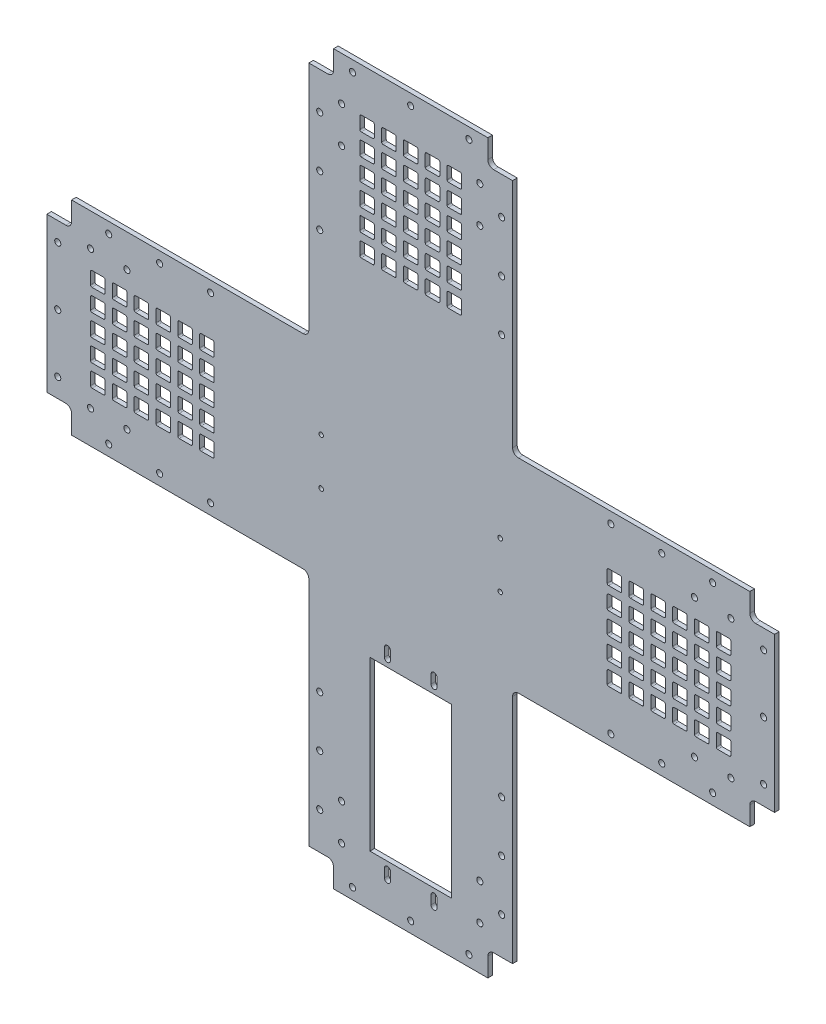
SolidWorks part; units mm, degrees
ref_plane "Front Plane" through (0, 0, 0) normal (0, 0, 1) x (1, 0, 0)
ref_plane "Top Plane" through (0, 0, 0) normal (0, 1, 0) x (1, 0, 0)
ref_plane "Right Plane" through (0, 0, 0) normal (1, 0, 0) x (0, 0, -1)
sketch "Sketch1" plane through (0, 0, 0) normal (0, 0, 1) x (1, 0, 0)
  line L0 (0, 0) -> (0, 180)
  line L1 (0, 180) -> (140, 180)
  line L2 (140, 180) -> (140, 0)
  line L3 (140, 0) -> (320, 0)
  line L4 (320, 0) -> (320, -140)
  line L5 (320, -140) -> (140, -140)
  line L6 (140, -140) -> (140, -320)
  line L7 (140, -320) -> (0, -320)
  line L8 (0, -320) -> (0, -140)
  line L9 (0, -140) -> (-180, -140)
  line L10 (-180, -140) -> (-180, 0)
  line L11 (-180, 0) -> (0, 0)
  line L12 (70, 180) -> (70, -320) construction
  line L13 (0, 180) -> (17, 180)
  line L14 (0, 180) -> (0, 163)
  line L15 (0, 163) -> (17, 163)
  line L16 (17, 180) -> (17, 163)
  line L17 (-180, -70) -> (320, -70) construction
  line L18 (140, 0) -> (0, -140) construction
  line L19 (0, 0) -> (140, -140) construction
  line L20 (7.5, 137.5) -> (7.5, 67.5) construction
  line L21 (140, 180) -> (123, 180)
  line L22 (140, 180) -> (140, 163)
  line L23 (140, 163) -> (123, 163)
  line L24 (123, 180) -> (123, 163)
  line L25 (-180, 0) -> (-163, 0)
  line L26 (-180, 0) -> (-180, -17)
  line L27 (-180, -17) -> (-163, -17)
  line L28 (-163, 0) -> (-163, -17)
  line L29 (-180, -140) -> (-163, -140)
  line L30 (-180, -140) -> (-180, -123)
  line L31 (-180, -123) -> (-163, -123)
  line L32 (-163, -140) -> (-163, -123)
  line L33 (320, 0) -> (303, 0)
  line L34 (320, 0) -> (320, -17)
  line L35 (320, -17) -> (303, -17)
  line L36 (303, 0) -> (303, -17)
  line L37 (320, -140) -> (303, -140)
  line L38 (320, -140) -> (320, -123)
  line L39 (320, -123) -> (303, -123)
  line L40 (303, -140) -> (303, -123)
  line L41 (140, -320) -> (123, -320)
  line L42 (140, -320) -> (140, -303)
  line L43 (140, -303) -> (123, -303)
  line L44 (123, -320) -> (123, -303)
  line L45 (0, -320) -> (17, -320)
  line L46 (0, -320) -> (0, -303)
  line L47 (0, -303) -> (17, -303)
  line L48 (17, -320) -> (17, -303)
  line L49 (22.5, 150) -> (117.5, 150) construction
  line L50 (22.5, 150) -> (22.5, 125) construction
  line L51 (22.5, 125) -> (117.5, 125) construction
  line L52 (117.5, 150) -> (117.5, 125) construction
  line L53 (30, 172.5) -> (110, 172.5) construction
  line L64 (42, -227.325) -> (98, -227.325) construction
  line L69 (42, -169.65) -> (98, -169.65)
  line L70 (42, -169.65) -> (42, -285)
  line L71 (42, -285) -> (98, -285)
  line L72 (98, -169.65) -> (98, -285)
  line L73 (51.95, -290) -> (56.05, -290) construction
  line L74 (51.95, -290) -> (51.95, -296)
  line L75 (51.95, -296) -> (56.05, -296) construction
  line L76 (56.05, -290) -> (56.05, -296)
  line L77 (88.05, -290) -> (88.05, -296)
  line L78 (83.95, -290) -> (83.95, -296)
  line L79 (88.05, -164.65) -> (88.05, -158.65)
  line L80 (83.95, -164.65) -> (83.95, -158.65)
  line L81 (51.95, -164.65) -> (51.95, -158.65)
  line L82 (56.05, -164.65) -> (56.05, -158.65)
  line L83 (8.5, -54) -> (131.5, -86) construction
  line L84 (8.5, -54) -> (131.5, -54) construction
  line L85 (8.5, -54) -> (8.5, -86) construction
  line L86 (8.5, -86) -> (131.5, -86) construction
  line L87 (131.5, -54) -> (131.5, -86) construction
  line L88 (131.5, -54) -> (8.5, -86) construction
  circle A0 centre (22.5, 150) radius 2.1
  circle A1 centre (22.5, 125) radius 2.1
  circle A2 centre (117.5, 150) radius 2.1
  circle A3 centre (117.5, 125) radius 2.1
  circle A4 centre (-125, -117.5) radius 2.1
  circle A5 centre (-150, -117.5) radius 2.1
  circle A6 centre (-125, -22.5) radius 2.1
  circle A7 centre (-150, -22.5) radius 2.1
  circle A8 centre (265, -117.5) radius 2.1
  circle A9 centre (265, -22.5) radius 2.1
  circle A10 centre (290, -22.5) radius 2.1
  circle A11 centre (290, -117.5) radius 2.1
  circle A12 centre (117.5, -290) radius 2.1
  circle A13 centre (117.5, -265) radius 2.1
  circle A14 centre (22.5, -265) radius 2.1
  circle A15 centre (22.5, -290) radius 2.1
  circle A17 centre (7.5, 137.5) radius 2.1
  circle A18 centre (7.5, 67.5) radius 2.1
  circle A19 centre (7.5, 102.5) radius 2.1
  circle A20 centre (30, 172.5) radius 2.1
  circle A21 centre (70, 172.5) radius 2.1
  circle A22 centre (110, 172.5) radius 2.1
  circle A23 centre (132.5, 67.5) radius 2.1
  circle A24 centre (132.5, 102.5) radius 2.1
  circle A25 centre (132.5, 137.5) radius 2.1
  circle A26 centre (207.5, -7.5) radius 2.1
  circle A27 centre (242.5, -7.5) radius 2.1
  circle A28 centre (277.5, -7.5) radius 2.1
  circle A29 centre (312.5, -30) radius 2.1
  circle A30 centre (312.5, -70) radius 2.1
  circle A31 centre (312.5, -110) radius 2.1
  circle A32 centre (277.5, -132.5) radius 2.1
  circle A33 centre (242.5, -132.5) radius 2.1
  circle A34 centre (207.5, -132.5) radius 2.1
  circle A35 centre (-67.5, -132.5) radius 2.1
  circle A36 centre (-102.5, -132.5) radius 2.1
  circle A37 centre (-137.5, -132.5) radius 2.1
  circle A38 centre (-172.5, -110) radius 2.1
  circle A39 centre (-172.5, -70) radius 2.1
  circle A40 centre (-172.5, -30) radius 2.1
  circle A41 centre (-137.5, -7.5) radius 2.1
  circle A42 centre (-102.5, -7.5) radius 2.1
  circle A43 centre (-67.5, -7.5) radius 2.1
  circle A44 centre (7.5, -207.5) radius 2.1
  circle A45 centre (7.5, -242.5) radius 2.1
  circle A46 centre (7.5, -277.5) radius 2.1
  circle A47 centre (30, -312.5) radius 2.1
  circle A48 centre (70, -312.5) radius 2.1
  circle A49 centre (110, -312.5) radius 2.1
  circle A50 centre (132.5, -277.5) radius 2.1
  circle A51 centre (132.5, -242.5) radius 2.1
  circle A52 centre (132.5, -207.5) radius 2.1
  arc A53 (51.95, -290) -> (56.05, -290) centre (54, -290) cw
  arc A54 (51.95, -296) -> (56.05, -296) centre (54, -296) ccw
  arc A55 (88.05, -296) -> (83.95, -296) centre (86, -296) cw
  arc A56 (88.05, -290) -> (83.95, -290) centre (86, -290) ccw
  arc A57 (88.05, -158.65) -> (83.95, -158.65) centre (86, -158.65) ccw
  arc A58 (88.05, -164.65) -> (83.95, -164.65) centre (86, -164.65) cw
  arc A59 (51.95, -158.65) -> (56.05, -158.65) centre (54, -158.65) cw
  arc A60 (51.95, -164.65) -> (56.05, -164.65) centre (54, -164.65) ccw
  circle A61 centre (8.5, -54) radius 1.55
  circle A62 centre (131.5, -54) radius 1.55
  circle A63 centre (131.5, -86) radius 1.55
  circle A64 centre (8.5, -86) radius 1.55
  point P21 (70, -320)
  point P24 (320, -70)
  point P147 (70, -169.65)
  point P197 (70, -70)
  point P198 (70, -70)
  dimension "D29" = 4.2
  dimension "D30" = 4.2
  dimension "D31" = 4.2
  dimension "D32" = 4.2
  dimension "D33" = 4.2
  dimension "D34" = 4.2
  dimension "D35" = 4.2
  dimension "D42" = 4.2
  dimension "D43" = 4.2
  dimension "D44" = 4.2
  dimension "D59" = 3.1
  dimension "D60" = 3.1
  dimension "D61" = 3.1
  dimension "D62" = 3.1
  dimension "D1" = 140
  dimension "D2" = 140
  dimension "D3" = 140
  dimension "D4" = 140
  dimension "D5" = 180
  dimension "D6" = 180
  dimension "D7" = 180
  dimension "D8" = 180
  dimension "D9" = 17
  dimension "D10" = 17
  dimension "D11" = 17
  dimension "D12" = 17
  dimension "D13" = 17
  dimension "D14" = 17
  dimension "D15" = 17
  dimension "D16" = 17
  dimension "D17" = 17
  dimension "D18" = 17
  dimension "D19" = 17
  dimension "D20" = 17
  dimension "D21" = 17
  dimension "D22" = 17
  dimension "D23" = 17
  dimension "D24" = 17
  dimension "D25" = 95
  dimension "D26" = 25
  dimension "D27" = 22.5
  dimension "D28" = 30
  dimension "D36" = 42.5
  dimension "D37" = 70
  dimension "D38" = 7.5
  dimension "D39" = 80
  dimension "D40" = 30
  dimension "D41" = 7.5
  dimension "D49" = 56
  dimension "D51" = 20
  dimension "D52" = 115.35
  dimension "D53" = 5
  dimension "D54" = 16
  dimension "D55" = 4.1
  dimension "D56" = 6
  dimension "D57" = 123
  dimension "D58" = 32
extrude "Boss-Extrude1" add sketch "Sketch1" along normal blind 3.175 contours L48 L7 L44 L43 L6 L5 L40 L39 L4 L35 L36 L3 L2 L23 L24 L1 L16 L15 L0 L11 L28 L27 L10 L31 L32 L9 L8 L47 A52 A51 A50 A48 A46 A44 A42 A40 A38 A37 A36
fillet "Fillet1" radius 4 12 edges at (17, 163, 1.5875) (0, 0, 1.5875) (-163, -17, 1.5875) (-163, -123, 1.5875) (0, -140, 1.5875) (17, -303, 1.5875) (123, -303, 1.5875) (140, -140, 1.5875) (303, -123, 1.5875) (303, -17, 1.5875) (140, 0, 1.5875) (123, 163, 1.5875)
ref_point "Point1"
sketch "Sketch2" plane through (0, 0, 3.175) normal (0, 0, 1) x (1, 0, 0)
  line L1 (35, 150) -> (45, 150)
  line L2 (35, 150) -> (35, 140)
  line L3 (35, 140) -> (45, 140)
  line L4 (45, 150) -> (45, 140)
  line L5 (35, 150) -> (45, 140) construction
  line L6 (35, 140) -> (45, 150) construction
  line L7 (17, 180) -> (123, 180) construction
  line L8 (70, 180) -> (70, -109.3094) construction
  point P0 (40, 145)
  dimension "D1" = 10
  dimension "D2" = 10
  dimension "D3" = 30
  dimension "D4" = 35
extrude "Cut-Extrude1" cut sketch "Sketch2" against normal blind 10
fillet "Fillet2" radius 1 4 edges at (45, 140, 1.5875) (35, 140, 1.5875) (45, 150, 1.5875) (35, 150, 1.5875)
pattern_linear "LPattern2" count 5 spacing 15 along (1, 0, 0) count 6 spacing 15 along (0, -1, 0) of "Cut-Extrude1", "Fillet2"
sketch "Sketch6" plane through (0, 0, 3.175) normal (0, 0, 1) x (1, 0, 0)
  line L1 (-150, -95) -> (-140, -95)
  line L2 (-150, -95) -> (-150, -105)
  line L3 (-150, -105) -> (-140, -105)
  line L4 (-140, -95) -> (-140, -105)
  line L5 (-150, -95) -> (-140, -105) construction
  line L6 (-150, -105) -> (-140, -95) construction
  line L7 (-180, -123) -> (-180, -17) construction
  line L8 (-180, -70) -> (320, -70) construction
  point P0 (-145, -100)
  dimension "D1" = 10
  dimension "D2" = 10
  dimension "D3" = 30
  dimension "D4" = 35
extrude "Cut-Extrude2" cut sketch "Sketch6" against normal blind 10
fillet "Fillet3" radius 1 4 edges at (-150, -105, 1.5875) (-140, -105, 1.5875) (-140, -95, 1.5875) (-150, -95, 1.5875)
pattern_linear "LPattern5" count 5 spacing 15 along (0, 1, 0) count 6 spacing 15 along (1, 0, 0) of "Cut-Extrude2", "Fillet3"
ref_plane "Plane1" through (0, 0, 0) normal (0, 0, 1) x (0, -1, 0)
sketch "Sketch9" plane through (0, 0, 3.175) normal (0, 0, 1) x (1, 0, 0)
  line L0 (-180, -70) -> (320, -70) construction
  line L1 (280, -95) -> (290, -95)
  line L2 (280, -95) -> (280, -105)
  line L3 (280, -105) -> (290, -105)
  line L4 (290, -95) -> (290, -105)
  line L5 (280, -95) -> (290, -105) construction
  line L6 (280, -105) -> (290, -95) construction
  line L7 (320, 0) -> (320, -140) construction
  point P0 (285, -100)
  dimension "D1" = 10
  dimension "D2" = 10
  dimension "D3" = 30
  dimension "D4" = 35
extrude "Cut-Extrude10" cut sketch "Sketch9" against normal blind 5
fillet "Fillet4" radius 1 4 edges at (290, -105, 1.5875) (280, -105, 1.5875) (290, -95, 1.5875) (280, -95, 1.5875)
pattern_linear "LPattern6" count 5 spacing 15 along (0, 1, 0) count 6 spacing 15 along (-1, 0, 0) of "Cut-Extrude10", "Fillet4"
